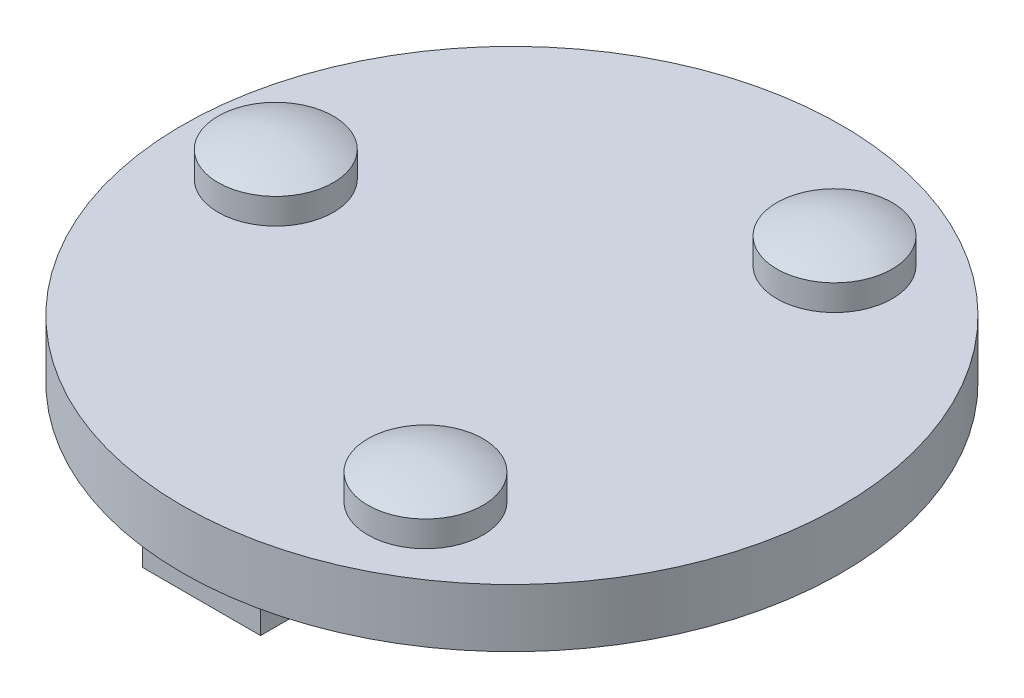
SolidWorks part; units mm, degrees
ref_plane "Front Plane" through (0, 0, 0) normal (0, 0, 1) x (1, 0, 0)
ref_plane "Top Plane" through (0, 0, 0) normal (0, 1, 0) x (1, 0, 0)
ref_plane "Right Plane" through (0, 0, 0) normal (1, 0, 0) x (0, 0, -1)
sketch "Sketch1" plane through (0, 0, 0) normal (0, 1, 0) x (1, 0, 0)
  circle A0 centre (0, 0) radius 15.35
  dimension "D1" = 30.7
extrude "Boss-Extrude1" add sketch "Sketch1" along normal blind 2.71
sketch "Sketch2" plane through (0, 2.71, 0) normal (0, 1, 0) x (-1, 0, 0)
  line L1 (-5.5, 9.5263) -> (0, 0) construction
  line L2 (0, 1.4905) -> (0, -1.4905) construction
  circle A0 centre (-5.5, 9.5263) radius 2.685
  dimension "D1" = 5.37
  dimension "D2" = 11
  dimension "D3" = 30
extrude "Boss-Extrude2" add sketch "Sketch2" along normal blind 1.2
dome "Dome1" faces to dome 1 distance 0.6 reverse direction no elliptical dome no face at (5.5, 3.91, 12.2113) parameters "D1"=0.6
pattern_circular "CirPattern1" count 3 over 360 about axis through (0, 2.71, 0) along (0, 1, 0) of "Dome1", "Boss-Extrude2"
sketch "Sketch3" plane through (0, 0, 0) normal (0, -1, 0) x (1, 0, 0)
  line L0 (0, 15.35) -> (0, -15.35) construction
  line L1 (0, -1.4905) -> (0, 1.4905) construction
  line L2 (2.75, 14.4577) -> (-2.75, 14.4577)
  line L3 (2.75, 14.4577) -> (2.75, 10.2577)
  line L4 (2.75, 10.2577) -> (-2.75, 10.2577)
  line L5 (-2.75, 14.4577) -> (-2.75, 10.2577)
  line L6 (2.75, 14.4577) -> (-2.75, 10.2577) construction
  line L7 (2.75, 10.2577) -> (-2.75, 14.4577) construction
  line L8 (-2.75, 12.3577) -> (4.4429, 12.3577) construction
  line L9 (2.75, 13.7577) -> (4.25, 13.7577)
  line L10 (4.25, 13.7577) -> (4.25, 10.9577)
  line L11 (4.25, 10.9577) -> (2.75, 10.9577)
  line L12 (-4.25, 10.9577) -> (-2.75, 10.9577)
  line L13 (-4.25, 13.7577) -> (-4.25, 10.9577)
  line L14 (-2.75, 13.7577) -> (-4.25, 13.7577)
  line L15 (0, 0) -> (-15.35, 0) construction
  line L16 (2.75, -13.7577) -> (4.25, -13.7577)
  line L17 (4.25, -13.7577) -> (4.25, -10.9577)
  line L18 (4.25, -10.9577) -> (2.75, -10.9577)
  line L19 (2.75, -14.4577) -> (2.75, -10.2577)
  line L20 (2.75, -10.2577) -> (-2.75, -10.2577)
  line L21 (-4.25, -10.9577) -> (-2.75, -10.9577)
  line L22 (-4.25, -13.7577) -> (-4.25, -10.9577)
  line L23 (-2.75, -13.7577) -> (-4.25, -13.7577)
  line L24 (-2.75, -14.4577) -> (-2.75, -10.2577)
  line L25 (2.75, -14.4577) -> (-2.75, -14.4577)
  point P4 (0, 12.3577)
  point P16 (4.25, 12.3577)
  dimension "D1" = 5.5
  dimension "D2" = 0
  dimension "D3" = 4.2
  dimension "D4" = 2.8
  dimension "D5" = 1.5
extrude "Boss-Extrude3" add sketch "Sketch3" along normal blind 1.6 contours L2 L5 L4 L3 | L25 L19 L20 L24 region at (0, 0, 12.3577) region at (0, 0, -12.3577)
